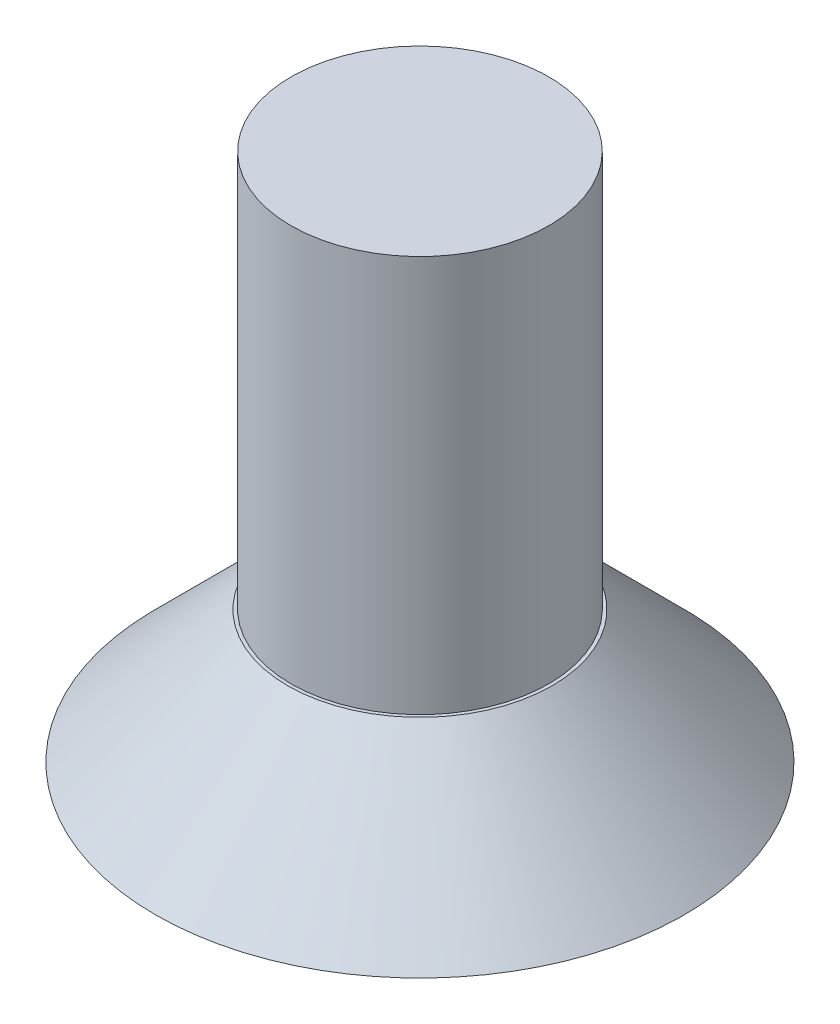
SolidWorks part; units mm, degrees
material "Plain Carbon Steel"
ref_plane "Front Plane" through (0, 0, 0) normal (0, 0, 1) x (1, 0, 0)
ref_plane "Top Plane" through (0, 0, 0) normal (0, 1, 0) x (1, 0, 0)
ref_plane "Right Plane" through (0, 0, 0) normal (1, 0, 0) x (0, 0, -1)
sketch "Sketch1" plane through (0, 0, 0) normal (0, 1, 0) x (1, 0, 0)
  circle A0 centre (0, 0) radius 4
  dimension "D1" = 8
extrude "Boss-Extrude1" add sketch "Sketch1" along normal blind 2
sketch "Sketch2" plane through (0, 2, 0) normal (0, 1, 0) x (1, 0, 0)
  circle A0 centre (0, 0) radius 1.95
  dimension "D1" = 3.9
extrude "Boss-Extrude2" add sketch "Sketch2" along normal blind 6
chamfer "Chamfer1" distance 2 angle 45 1 edges at (0, 2, 4)
sketch "Sketch3" plane through (0, 0, 0) normal (0, -1, 0) x (1, 0, 0)
  line L1 (0, -1.6625) -> (1.4397, -0.8312)
  line L2 (1.4397, -0.8312) -> (1.4397, 0.8312)
  line L3 (1.4397, 0.8312) -> (0, 1.6625)
  line L4 (0, 1.6625) -> (-1.4397, 0.8312)
  line L5 (-1.4397, 0.8312) -> (-1.4397, -0.8312)
  line L6 (-1.4397, -0.8312) -> (0, -1.6625)
  circle A0 centre (0, 0) radius 1.4397 construction
extrude "Cut-Extrude1" cut sketch "Sketch3" against normal blind 1.5
